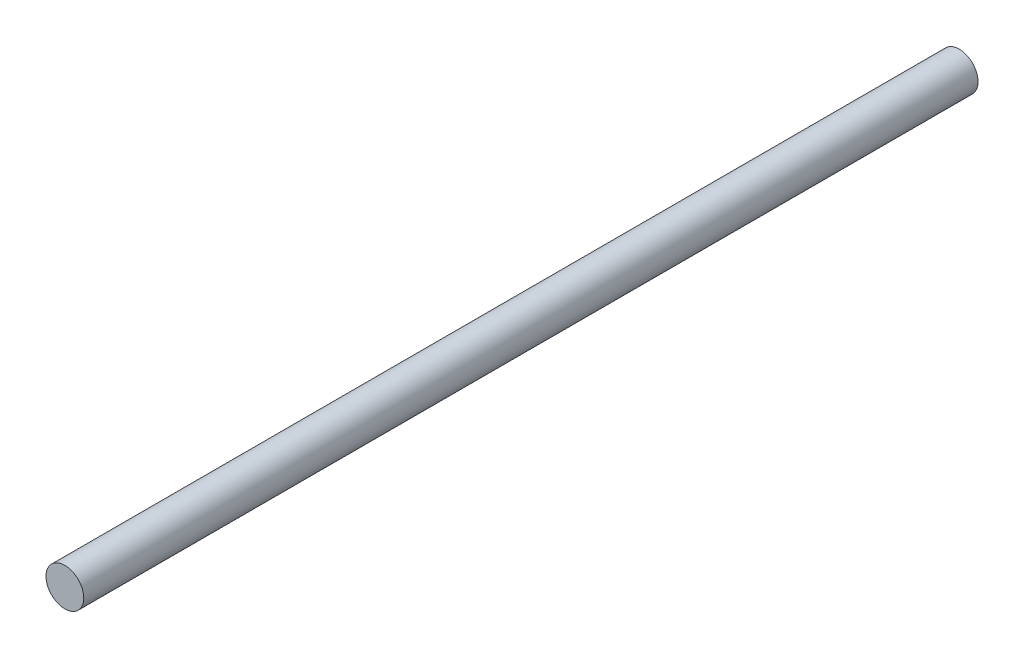
SolidWorks part; units mm, degrees
material "1.7036 (28CrS4)"
ref_plane "정면" through (0, 0, 0) normal (0, 0, 1) x (1, 0, 0)
ref_plane "윗면" through (0, 0, 0) normal (0, 1, 0) x (1, 0, 0)
ref_plane "우측면" through (0, 0, 0) normal (1, 0, 0) x (0, 0, -1)
sketch "스케치1" plane through (0, 0, 0) normal (0, 0, 1) x (1, 0, 0)
  circle A0 centre (0, 0) radius 5
  dimension "D1" = 10
extrude "보스-돌출1" add sketch "스케치1" along normal blind 208.44
sketch "스케치2" plane through (0, 0, 208.44) normal (0, 0, 1) x (1, 0, 0)
  text T0 "TEST\r\n"
  point P1 (0, 0)
sketch "스케치3" plane through (0, 0, 0) normal (0, 0, -1) x (-1, 0, 0)
  circle A0 centre (0, 0) radius 5
  dimension "D1" = 10
extrude "보스-돌출2" add sketch "스케치3" along normal blind 28.36
equation "\"`\"=4"
